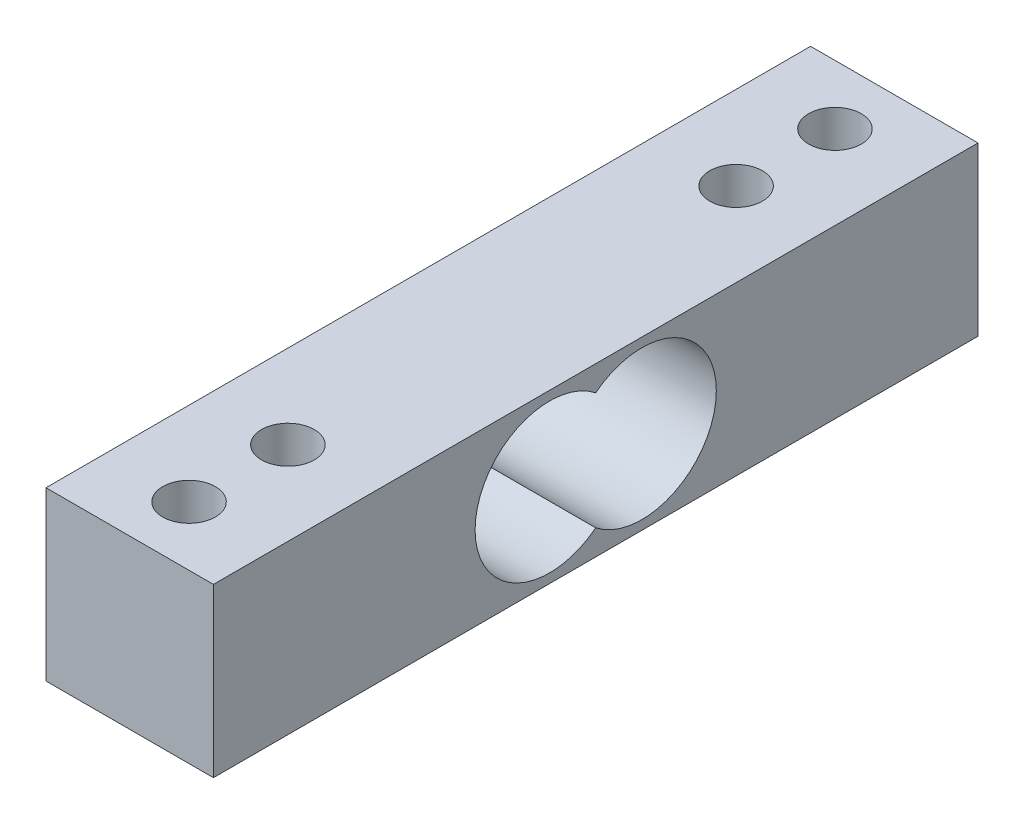
SolidWorks part; units mm, degrees
ref_plane "Plan de face" through (0, 0, 0) normal (0, 0, 1) x (1, 0, 0)
ref_plane "Plan de dessus" through (0, 0, 0) normal (0, 1, 0) x (1, 0, 0)
ref_plane "Plan de droite" through (0, 0, 0) normal (1, 0, 0) x (0, 0, -1)
sketch "Esquisse1" plane through (0, 0, 0) normal (0, 0, 1) x (1, 0, 0)
  line L0 (0, 19.2175) -> (0, -29.9729) construction
  line L1 (-6.35, 6.35) -> (6.35, 6.35)
  line L2 (-6.35, 6.35) -> (-6.35, -6.35)
  line L3 (-6.35, -6.35) -> (6.35, -6.35)
  line L4 (6.35, 6.35) -> (6.35, -6.35)
  line L5 (-22.701, 0) -> (33.2907, 0) construction
  dimension "D1" = 12.7
extrude "Boss.-Extru.1" add sketch "Esquisse1" against normal mid plane 58
sketch "Esquisse2" plane through (0, 6.35, 0) normal (0, 1, 0) x (1, 0, 0)
  line L0 (0, 29) -> (0, -29) construction
  line L1 (6.35, 29) -> (-6.35, 29) construction
  line L2 (6.35, -29) -> (-6.35, -29) construction
  line L3 (-6.35, 0) -> (6.35, 0) construction
  line L4 (-6.35, 29) -> (-6.35, -29) construction
  line L5 (6.35, 29) -> (6.35, -29) construction
  circle A0 centre (0, 24.5) radius 2
  circle A1 centre (0, 17) radius 2
  circle A2 centre (0, -17) radius 2
  circle A3 centre (0, -24.5) radius 2
  dimension "D3" = 4
  dimension "7" = 7.5
  dimension "D2" = 34
extrude "Enlèv. mat.-Extru.1" cut sketch "Esquisse2" against normal through all
sketch "Esquisse3" plane through (6.35, 0, 0) normal (1, 0, 0) x (0, 0, -1)
  line L0 (-29, 0) -> (29, 0) construction
  line L1 (-29, -6.35) -> (-29, 6.35) construction
  line L2 (29, -6.35) -> (29, 6.35) construction
  line L3 (0, 6.35) -> (0, -6.35) construction
  line L4 (29, 6.35) -> (-29, 6.35) construction
  line L5 (29, -6.35) -> (-29, -6.35) construction
  arc A0 (0, 4.4354) -> (0, -4.4354) centre (-3.5, 0) ccw
  arc A1 (0, -4.4354) -> (0, 4.4354) centre (3.5, 0) ccw
  dimension "D2" = 11.3
  dimension "D1" = 7
extrude "Enlèv. mat.-Extru.2" cut sketch "Esquisse3" against normal through all
ref_axis "Axe1" through (0, 0, -32.45) along (0, 0, 1)
ref_axis "Axe2" through (10.725, 0, 0) along (-1, 0, 0)
ref_plane "Plan1" through (0, 0, 24.5) normal (0, 0, -1) x (-1, 0, 0)
ref_plane "Plan2" through (0, 0, 17) normal (0, 0, -1) x (-1, 0, 0)
ref_plane "Plan3" through (0, 0, 20.75) normal (0, 0, -1) x (-1, 0, 0)
ref_axis "Axe3" through (0, -6.35, 24.5) along (0, 1, 0)
ref_plane "Plan4" through (0, 0, -17) normal (0, 0, -1) x (-1, 0, 0)
ref_plane "Plan5" through (0, 0, -24.5) normal (0, 0, -1) x (-1, 0, 0)
ref_plane "Plan6" through (0, 0, -20.75) normal (0, 0, -1) x (-1, 0, 0)
ref_axis "Axe4" through (0, -6.35, -24.5) along (0, 1, 0)
